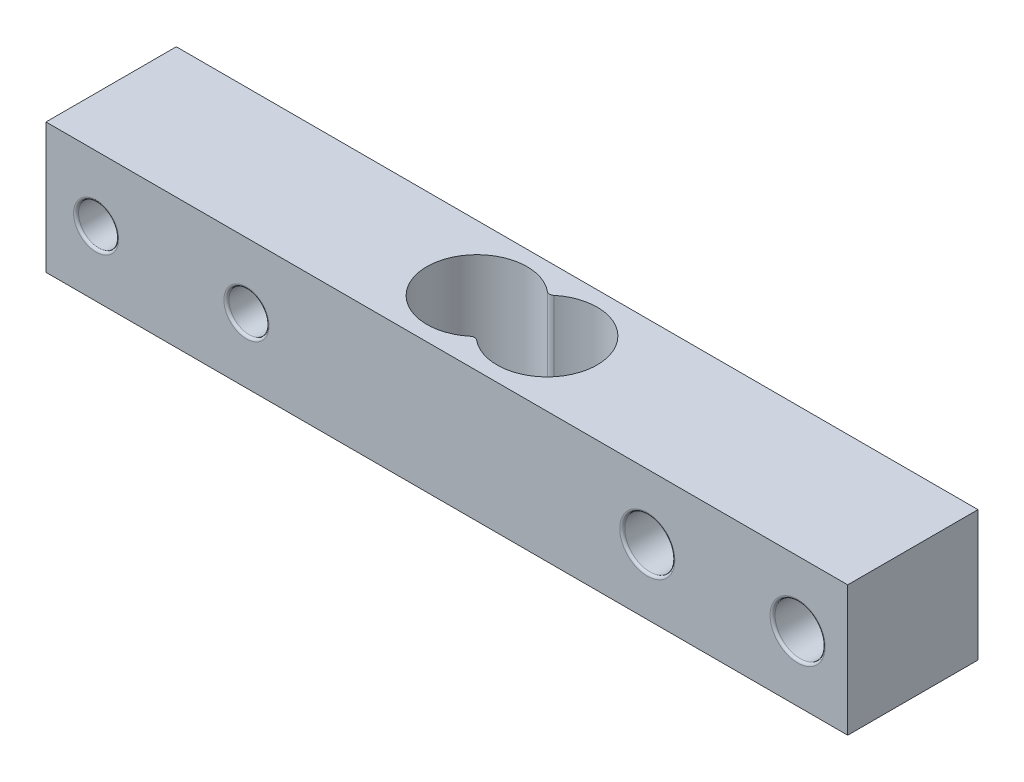
SolidWorks part; units mm, degrees
ref_plane "Front Plane" through (0, 0, 0) normal (0, 0, 1) x (1, 0, 0)
ref_plane "Top Plane" through (0, 0, 0) normal (0, 1, 0) x (1, 0, 0)
ref_plane "Right Plane" through (0, 0, 0) normal (1, 0, 0) x (0, 0, -1)
ref_plane "Plane1" through (0, 0, 0) normal (0, -1, 0) x (1, 0, 0)
sketch "Sketch1" plane through (0, 0, 0) normal (0, -1, 0) x (1, 0, 0)
  line L0 (52.0209, -0.5539) -> (-27.9791, -0.5539)
  line L1 (-27.9791, -0.5539) -> (-27.9791, -13.5539)
  line L2 (-27.9791, -13.5539) -> (52.0209, -13.5539)
  line L3 (52.0209, -13.5539) -> (52.0209, -0.5539)
extrude "Boss-Extrude1" add sketch "Sketch1" against normal blind 13
hole_wizard "Ø5.0 (5) Diameter Hole1" positions "Sketch3" profile "Sketch2" hole size "Ø5.0" standard "ANSI Metric"
sketch "Sketch3" plane through (0, 0, -0.5539) normal (0, 0, 1) x (1, 0, 0)
  point P0 (32.0209, 6.5)
  point P1 (47.0209, 6.5)
sketch "Sketch2" plane through (32.0209, 6.5, -0.5539) normal (1, 0, 0) x (0, -1, 0)
  line L0 (0, 0) -> (0, 13)
  line L1 (0, 13) -> (2.5, 13)
  line L2 (2.5, 13) -> (2.5, 0)
  line L5 (2.5, 0) -> (0, 0)
  line L11 (0, -6.35) -> (0, 107.95) construction
  dimension "Thru Hole Dia." = 5
  dimension "Thru Hole Depth" = 13
hole_wizard "Ø4.0 (4) Diameter Hole1" positions "Sketch5" profile "Sketch4" hole size "Ø4.0" standard "ANSI Metric"
sketch "Sketch5" plane through (0, 0, -0.5539) normal (0, 0, 1) x (1, 0, 0)
  point P0 (-7.9791, 6.5)
sketch "Sketch4" plane through (-7.9791, 6.5, -0.5539) normal (1, 0, 0) x (0, -1, 0)
  line L0 (0, 0) -> (0, 13)
  line L1 (0, 13) -> (2, 13)
  line L2 (2, 13) -> (2, 0)
  line L5 (2, 0) -> (0, 0)
  line L11 (0, -6.35) -> (0, 107.95) construction
  dimension "Thru Hole Dia." = 4
  dimension "Thru Hole Depth" = 13
hole_wizard "Ø4.0 (4) Diameter Hole2" positions "Sketch7" profile "Sketch6" hole size "Ø4.0" standard "ANSI Metric"
sketch "Sketch7" plane through (0, 0, -13.5539) normal (0, 0, -1) x (-1, 0, 0)
  point P0 (22.9791, 6.5)
sketch "Sketch6" plane through (-22.9791, 6.5, -13.5539) normal (1, 0, 0) x (0, 1, 0)
  line L0 (0, 0) -> (0, 13)
  line L1 (0, 13) -> (2, 13)
  line L2 (2, 13) -> (2, 0)
  line L5 (2, 0) -> (0, 0)
  line L11 (0, -6.35) -> (0, 107.95) construction
  dimension "Thru Hole Dia." = 4
  dimension "Thru Hole Depth" = 13
hole_wizard "Ø10.0 (10) Diameter Hole1" positions "Sketch9" profile "Sketch8" hole size "Ø10.0" standard "ANSI Metric"
sketch "Sketch9" plane through (0, 13, 0) normal (0, 1, 0) x (1, 0, 0)
  point P0 (8.5209, 7.0539)
sketch "Sketch8" plane through (8.5209, 13, -7.0539) normal (1, 0, 0) x (0, 0, 1)
  line L0 (0, 0) -> (0, 13)
  line L1 (0, 13) -> (5, 13)
  line L2 (5, 13) -> (5, 0)
  line L5 (5, 0) -> (0, 0)
  line L11 (0, -6.35) -> (0, 107.95) construction
  dimension "Thru Hole Dia." = 10
  dimension "Thru Hole Depth" = 13
hole_wizard "Ø10.0 (10) Diameter Hole2" positions "Sketch11" profile "Sketch10" hole size "Ø10.0" standard "ANSI Metric"
sketch "Sketch11" plane through (0, 0, 0) normal (0, -1, 0) x (-1, 0, 0)
  point P0 (-15.5209, 7.0539)
sketch "Sketch10" plane through (15.5209, 0, -7.0539) normal (1, 0, 0) x (0, 0, -1)
  line L0 (0, 0) -> (0, 13)
  line L1 (0, 13) -> (5, 13)
  line L2 (5, 13) -> (5, 0)
  line L5 (5, 0) -> (0, 0)
  line L11 (0, -6.35) -> (0, 107.95) construction
  dimension "Thru Hole Dia." = 10
  dimension "Thru Hole Depth" = 13
fillet "Fillet1" radius 0.25 8 edges at (-5.9791, 6.5, -13.5539) (-5.9791, 6.5, -0.5539) (34.5209, 6.5, -13.5539) (49.5209, 6.5, -13.5539) (34.5209, 6.5, -0.5539) (-24.9791, 6.5, -0.5539) (49.5209, 6.5, -0.5539) (-24.9791, 6.5, -13.5539) tangent propagation no
fillet "Fillet2" radius 0.5 2 edges at (12.0209, 6.5, -10.6246) (12.0209, 6.5, -3.4831) tangent propagation no
